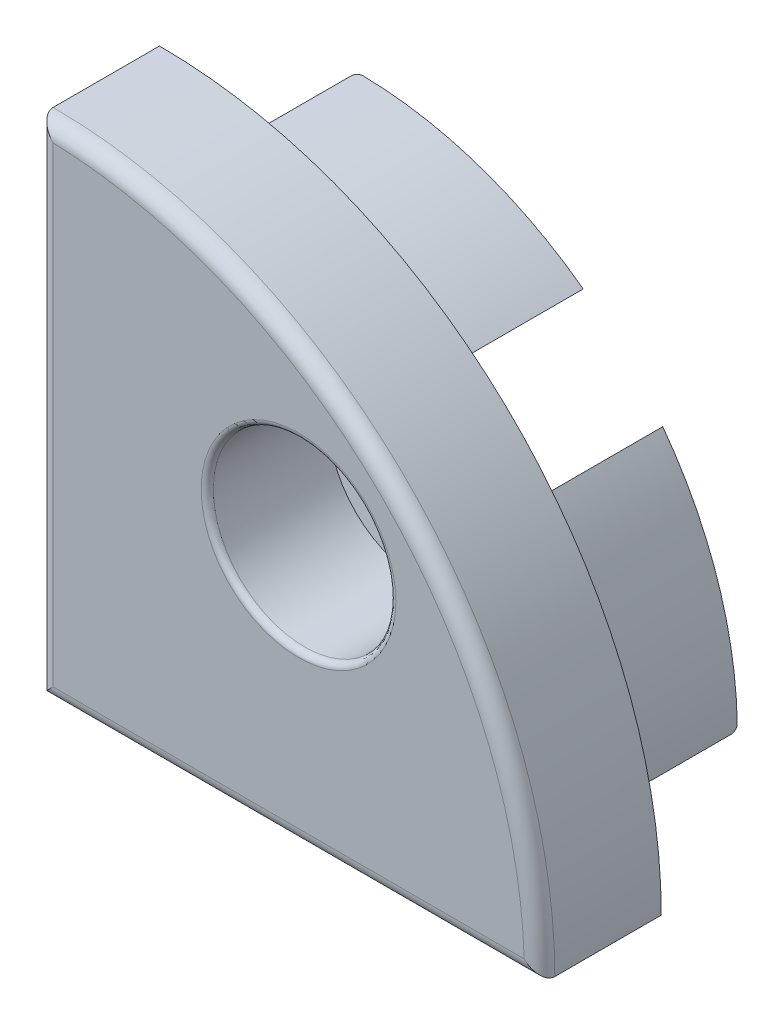
SolidWorks part; units mm, degrees
material "Nylon 101"
ref_plane "Front Plane" through (0, 0, 0) normal (0, 0, 1) x (1, 0, 0)
ref_plane "Top Plane" through (0, 0, 0) normal (0, 1, 0) x (1, 0, 0)
ref_plane "Right Plane" through (0, 0, 0) normal (1, 0, 0) x (0, 0, -1)
sketch "Sketch1" plane through (0, 0, 0) normal (0, 0, 1) x (1, 0, 0)
  line L0 (0, 0) -> (11.6673, 11.6673) construction
  line L1 (0, 0) -> (0, 16.5) construction
  line L2 (0, 0) -> (0, 16.5)
  line L3 (0, 0) -> (16.5, 0)
  arc A0 (0, 16.5) -> (16.5, 0) centre (0, 0) cw
  dimension "D1" = 16.5
  dimension "D2" = 45
extrude "Boss-Extrude2" add sketch "Sketch1" against normal blind 4 contours A0 L2 L3 region at (7.0028, 7.0028, 0)
fillet "Fillet1" radius 0.5 3 edges at (8.25, 0, 0) (0, 8.25, 0) (11.6673, 11.6673, 0)
sketch "Sketch2" plane through (0, 0, -4) normal (0, 0, -1) x (-1, 0, 0)
  line L0 (0, 0) -> (0, 16.5) construction
  line L3 (0, 0) -> (-16.5, 0) construction
  line L4 (0, 0) -> (-1.5, 1.5) construction
  line L5 (0, 1.5) -> (-1.5, 1.5) construction
  line L6 (-1.5, 1.5) -> (-1.5, 0) construction
  line L8 (-1.5, 14) -> (-1.5, 11.5)
  line L9 (-14, 1.5) -> (-11.5, 1.5)
  line L10 (-1.5, 1.5) -> (-1.5, 6.7962)
  line L11 (-1.5, 6.7962) -> (-6.7962, 1.5)
  line L12 (-6.7962, 1.5) -> (-1.5, 1.5)
  arc A0 (-1.5, 11.5) -> (-11.5, 1.5) centre (-1.5, 1.5) ccw
  arc A1 (-1.5, 14) -> (-14, 1.5) centre (-1.5, 1.5) ccw
  point P9 (0, 0)
  point P16 (0, 0)
  point P17 (0, 0)
  point P18 (0, 0)
  dimension "D3" = 10
  dimension "D4" = 45
  dimension "D6" = 12.5
  dimension "D1" = 1.5
  dimension "D2" = 1.5
  dimension "D5" = 7.49
extrude "Boss-Extrude3" add sketch "Sketch2" along normal blind 5 contours A0 L9 A1 L8
extrude "Extrude-Thin1" add sketch "Sketch2<3>" along normal blind 5 separate body thin contours L11 L12 L10 thin type one direction wall 0.5
sketch "Sketch2<3>" plane through (0, 0, -4) normal (0, 0, -1) x (-1, 0, 0) same geometry as "Sketch2"
fillet "Fillet5" radius 0.5 3 edges at (1, 1, -6.5) (1, 8.0033, -6.5) (8.0033, 1, -6.5)
fillet "Fillet6" radius 0.2 2 edges at (1.5, 12.75, -9) (12.75, 1.5, -9)
fillet "Fillet7" radius 0.2 6 edges at (7.2582, 1.3087, -9) (4.5017, 4.5017, -9) (1.3087, 7.2582, -9) (1, 4.1481, -9) (1.1464, 1.1464, -9) (4.1481, 1, -9)
sketch "Sketch4" plane through (0, 0, -4) normal (0, 0, -1) x (-1, 0, 0)
  circle A0 centre (-8.5711, 8.5711) radius 3
  arc A1 (-1.7, 11.498) -> (-11.498, 1.7) centre (-1.5, 1.5) ccw construction
  dimension "D1" = 6
extrude "Cut-Extrude1" cut sketch "Sketch4" against normal mid plane 15
fillet "Fillet8" radius 0.2 1 edges at (11.5711, 8.5711, 0)
